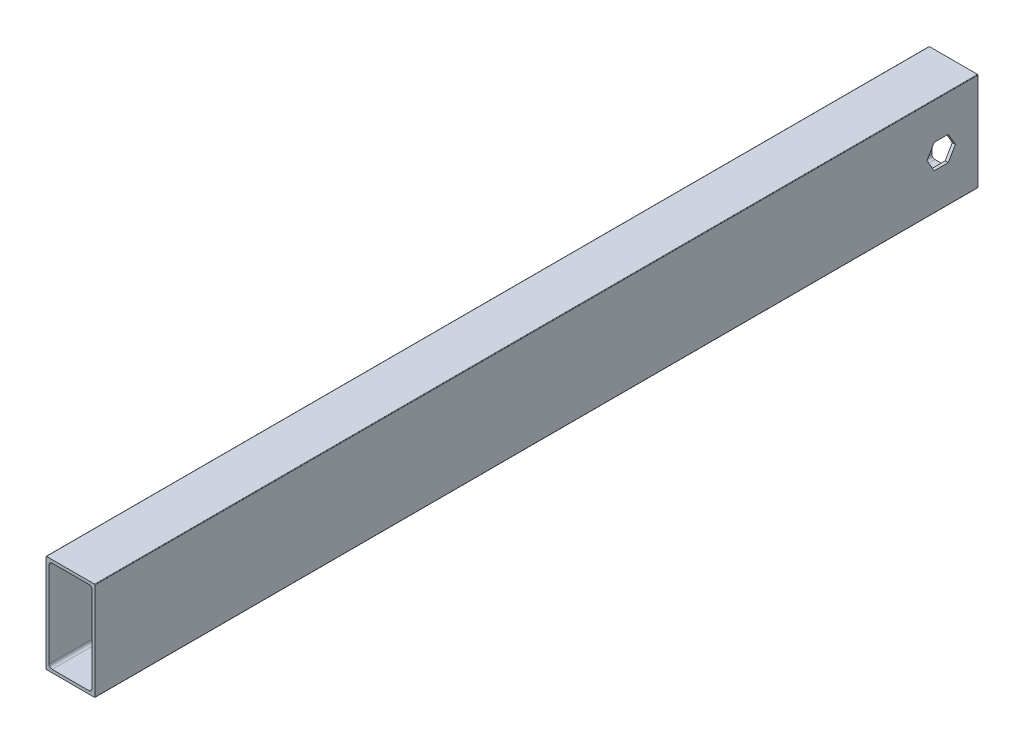
SolidWorks part; units mm, degrees
ref_plane "Front Plane" through (0, 0, 0) normal (0, 0, 1) x (1, 0, 0)
ref_plane "Top Plane" through (0, 0, 0) normal (0, 1, 0) x (1, 0, 0)
ref_plane "Right Plane" through (0, 0, 0) normal (1, 0, 0) x (0, 0, -1)
ref_plane "Plane1" through (0, 0, 0) normal (0, 0, -1) x (-1, 0, 0)
sketch "Sketch1" plane through (0, 0, 0) normal (0, 0, -1) x (-1, 0, 0)
  line L0 (-11.1125, -22.225) -> (-11.1125, 22.225)
  line L1 (-9.525, 23.8125) -> (9.525, 23.8125)
  line L2 (11.1125, 22.225) -> (11.1125, -22.225)
  line L3 (9.525, -23.8125) -> (-9.525, -23.8125)
  line L4 (-12.7, 25.146) -> (-12.7, -25.146)
  line L5 (-12.446, -25.4) -> (12.446, -25.4)
  line L6 (12.7, -25.146) -> (12.7, 25.146)
  line L7 (12.446, 25.4) -> (-12.446, 25.4)
  arc A0 (-11.1125, 22.225) -> (-9.525, 23.8125) centre (-9.525, 22.225) cw
  arc A1 (9.525, 23.8125) -> (11.1125, 22.225) centre (9.525, 22.225) cw
  arc A2 (11.1125, -22.225) -> (9.525, -23.8125) centre (9.525, -22.225) cw
  arc A3 (-9.525, -23.8125) -> (-11.1125, -22.225) centre (-9.525, -22.225) cw
  arc A4 (-12.7, -25.146) -> (-12.446, -25.4) centre (-12.446, -25.146) ccw
  arc A5 (12.446, -25.4) -> (12.7, -25.146) centre (12.446, -25.146) ccw
  arc A6 (12.7, 25.146) -> (12.446, 25.4) centre (12.446, 25.146) ccw
  arc A7 (-12.446, 25.4) -> (-12.7, 25.146) centre (-12.446, 25.146) ccw
extrude "Boss-Extrude1" add sketch "Sketch1" against normal blind 457.2
sketch "Sketch2" plane through (-12.7, 0, 0) normal (-1, 0, 0) x (0, 0, 1)
  line L0 (0, 0) -> (19.05, 0) construction
  line L2 (26.3823, 0) -> (22.7162, 6.35)
  line L3 (22.7162, 6.35) -> (15.3838, 6.35)
  line L4 (15.3838, 6.35) -> (11.7177, 0)
  line L5 (11.7177, 0) -> (15.3838, -6.35)
  line L6 (15.3838, -6.35) -> (22.7162, -6.35)
  line L7 (22.7162, -6.35) -> (26.3823, 0)
  circle A0 centre (19.05, 0) radius 6.35 construction
  dimension "D1" = 12.7
  dimension "D2" = 19.05
extrude "Cut-Extrude1" cut sketch "Sketch2" against normal blind 25.4
